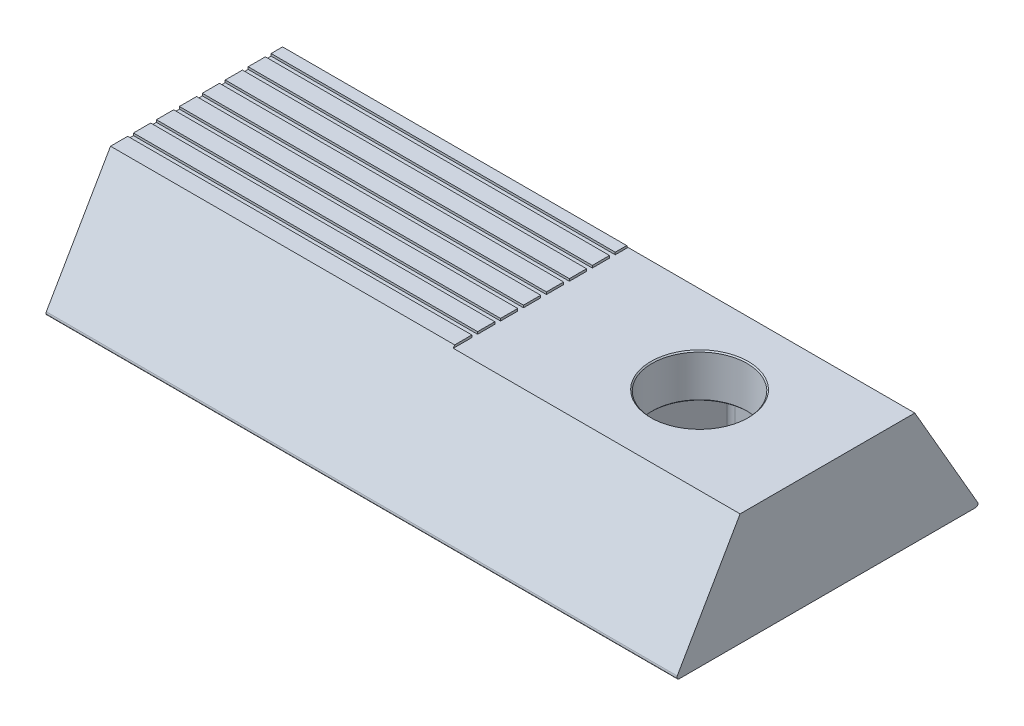
SolidWorks part; units mm, degrees
material "Copper"
ref_plane "Front Plane" through (0, 0, 0) normal (0, 0, 1) x (1, 0, 0)
ref_plane "Top Plane" through (0, 0, 0) normal (0, 1, 0) x (1, 0, 0)
ref_plane "Right Plane" through (0, 0, 0) normal (1, 0, 0) x (0, 0, -1)
sketch "Sketch1" plane through (0, 0, 0) normal (0, 1, 0) x (1, 0, 0)
  line L0 (15, 0) -> (0, 0) construction
  line L1 (-15, -7.5) -> (15, -7.5)
  line L2 (-15, -7.5) -> (-15, 7.5)
  line L3 (-15, 7.5) -> (15, 7.5)
  line L5 (0, 0) -> (0, -7.5) construction
  line L6 (15, -7.5) -> (15, 7.5) construction
  line L7 (15, -7.5) -> (40, -7.5)
  line L9 (15, 7.5) -> (40, 7.5)
  line L10 (40, -7.5) -> (40, 7.5)
  line L11 (0, 0) -> (-9, 0) construction
  line L12 (28.85, 0) -> (15, 0) construction
  circle A0 centre (28.85, 0) radius 4.15
  circle A1 centre (9, 0) radius 1.025 construction
  circle A2 centre (0, 0) radius 1.025 construction
  circle A3 centre (-9, 0) radius 1.025 construction
  dimension "D4" = 2.05
  dimension "D5" = 9
  dimension "D6" = 9
  dimension "D7" = 8.3
  dimension "D1" = 15
  dimension "D2" = 30
  dimension "D3" = 25
  dimension "D8" = 7
extrude "Boss-Extrude1" add sketch "Sketch1" along normal blind 10
sketch "Sketch2" plane through (0, 0, 0) normal (1, 0, 0) x (0, 0, -1)
  line L1 (-6, 10) -> (-5.5, 10)
  line L2 (-6, 10) -> (-6, 9.8)
  line L3 (-6, 9.8) -> (-5.5, 9.8)
  line L4 (-5.5, 10) -> (-5.5, 9.8)
  line L6 (-3.5, 10) -> (-3.5, 9.8)
  line L7 (-4, 10) -> (-3.5, 10)
  line L8 (-4, 10) -> (-4, 9.8)
  line L9 (-4, 9.8) -> (-3.5, 9.8)
  line L10 (-1.5, 10) -> (-1.5, 9.8)
  line L11 (-2, 10) -> (-1.5, 10)
  line L12 (-2, 10) -> (-2, 9.8)
  line L13 (-2, 9.8) -> (-1.5, 9.8)
  line L14 (0.5, 10) -> (0.5, 9.8)
  line L15 (0, 10) -> (0.5, 10)
  line L16 (0, 10) -> (0, 9.8)
  line L17 (0, 9.8) -> (0.5, 9.8)
  line L18 (2.5, 10) -> (2.5, 9.8)
  line L19 (2, 10) -> (2.5, 10)
  line L20 (2, 10) -> (2, 9.8)
  line L21 (2, 9.8) -> (2.5, 9.8)
  line L22 (4.5, 10) -> (4.5, 9.8)
  line L23 (4, 10) -> (4.5, 10)
  line L24 (4, 10) -> (4, 9.8)
  line L25 (4, 9.8) -> (4.5, 9.8)
  line L26 (6.5, 10) -> (6.5, 9.8)
  line L27 (6, 10) -> (6.5, 10)
  line L28 (6, 10) -> (6, 9.8)
  line L29 (6, 9.8) -> (6.5, 9.8)
  line L30 (-7.5, 10) -> (-7.5, 0) construction
  line L31 (7.5, 10) -> (-7.5, 10) construction
  dimension "D1" = 1.5
  dimension "D2" = 0.5
  dimension "D3" = 0.2
  dimension "D5" = 1.5
  dimension "D4" = 7
extrude "Cut-Extrude2" cut sketch "Sketch2" against normal through all both and the other way through all
sketch "Sketch3" plane through (0, 0, 0) normal (1, 0, 0) x (0, 0, -1)
  line L0 (7.5, 10) -> (13.0978, 0.3043)
  line L1 (12.9221, 0) -> (7.5, 0)
  line L3 (7.5, 0) -> (7.5, 10)
  line L4 (0, 0) -> (0, 14.3053) construction
  line L6 (-7.5, 0) -> (-7.5, 10)
  line L7 (-7.5, 10) -> (-13.0978, 0.3043)
  line L8 (-12.9221, 0) -> (-7.5, 0)
  line L9 (7.5, 10) -> (6.5, 10) construction
  line L10 (7.5, 10) -> (7.5, 0) construction
  arc A0 (12.9221, 0) -> (13.0978, 0.3043) centre (12.9221, 0.2029) ccw
  arc A1 (-12.9221, 0) -> (-13.0978, 0.3043) centre (-12.9221, 0.2029) cw
  point P6 (13.2735, 0)
  point P10 (-13.2735, 0)
  dimension "D2" = 26.25
  dimension "D3" = 0.2029
  dimension "D1" = 30
extrude "Boss-Extrude2" add sketch "Sketch3" along normal up to surface and the other way up to surface up to face at (40, 9.2875, -0.2187) other way up to face at (-15, 9.2875, -0.2187)
sketch "Sketch10" plane through (40, 0, 0) normal (1, 0, 0) x (0, 0, -1)
  line L0 (7.5, 10) -> (13.0978, 0.3043) construction
  line L5 (7.6155, 9.8) -> (-7.6155, 9.8)
  line L6 (7.6155, 9.8) -> (7.6155, 10)
  line L7 (7.6155, 10) -> (-7.6155, 10)
  line L8 (-7.6155, 9.8) -> (-7.6155, 10)
  line L9 (-7.5, 10) -> (-6, 10) construction
  line L10 (-6, 9.8) -> (-5.5, 9.8) construction
  line L11 (-13.0978, 0.3043) -> (-7.5, 10) construction
extrude "Cut-Extrude6" cut sketch "Sketch10" against normal blind 25
sketch "Sketch8" plane through (0, 0, 0) normal (0, -1, 0) x (1, 0, 0)
  line L3 (25.0395, -6.6) -> (32.6605, -6.6)
  line L5 (32.6605, -6.6) -> (36.471, 0)
  line L12 (36.471, 0) -> (32.6605, 6.6)
  line L13 (32.6605, 6.6) -> (25.0395, 6.6)
  line L14 (25.0395, 6.6) -> (21.229, 0)
  line L15 (21.229, 0) -> (25.0395, -6.6)
  circle A2 centre (28.85, 0) radius 4.15 construction
  circle A4 centre (28.85, 0) radius 6.6 construction
  dimension "D1" = 13.2
extrude "Cut-Extrude5" cut sketch "Sketch8" against normal blind 6
fillet "Fillet3" radius 0.5 6 edges at (32.6605, 3, -6.6) (25.0395, 3, -6.6) (21.229, 3, 0) (25.0395, 3, 6.6) (32.6605, 3, 6.6) (36.471, 3, 0)
chamfer "Chamfer1" distance 0.1 angle 45 2 edges at (28.85, 6, -4.15) (28.85, 9.8, -4.15)
